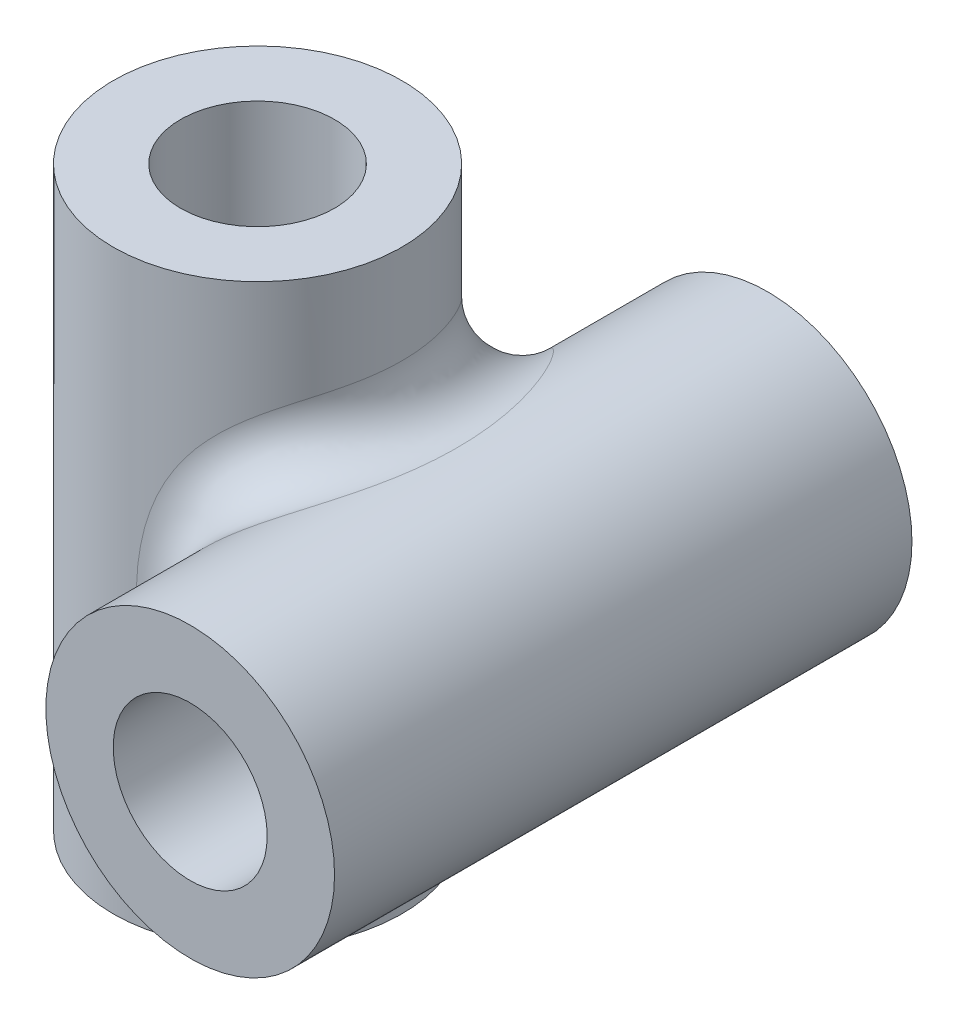
SolidWorks part; units mm, degrees
ref_plane "Front Plane" through (0, 0, 0) normal (0, 0, 1) x (1, 0, 0)
ref_plane "Top Plane" through (0, 0, 0) normal (0, 1, 0) x (1, 0, 0)
ref_plane "Right Plane" through (0, 0, 0) normal (1, 0, 0) x (0, 0, -1)
sketch "Sketch1" plane through (0, 0, 0) normal (0, 1, 0) x (1, 0, 0)
  circle A0 centre (0, 0) radius 8
  circle A1 centre (0, 0) radius 15
  dimension "D1" = 16
  dimension "D2" = 30
extrude "Boss-Extrude2" add sketch "Sketch1" along normal mid plane 60
sketch "Sketch3" plane through (0, 0, 0) normal (0, 0, 1) x (1, 0, 0)
  circle A0 centre (23, 0) radius 8
  circle A1 centre (23, 0) radius 15
  dimension "D1" = 23
extrude "Boss-Extrude3" add sketch "Sketch3" along normal mid plane 60
fillet "Fillet1" radius 5 1 edges at (8.3863, 3.3823, -12.4366)
